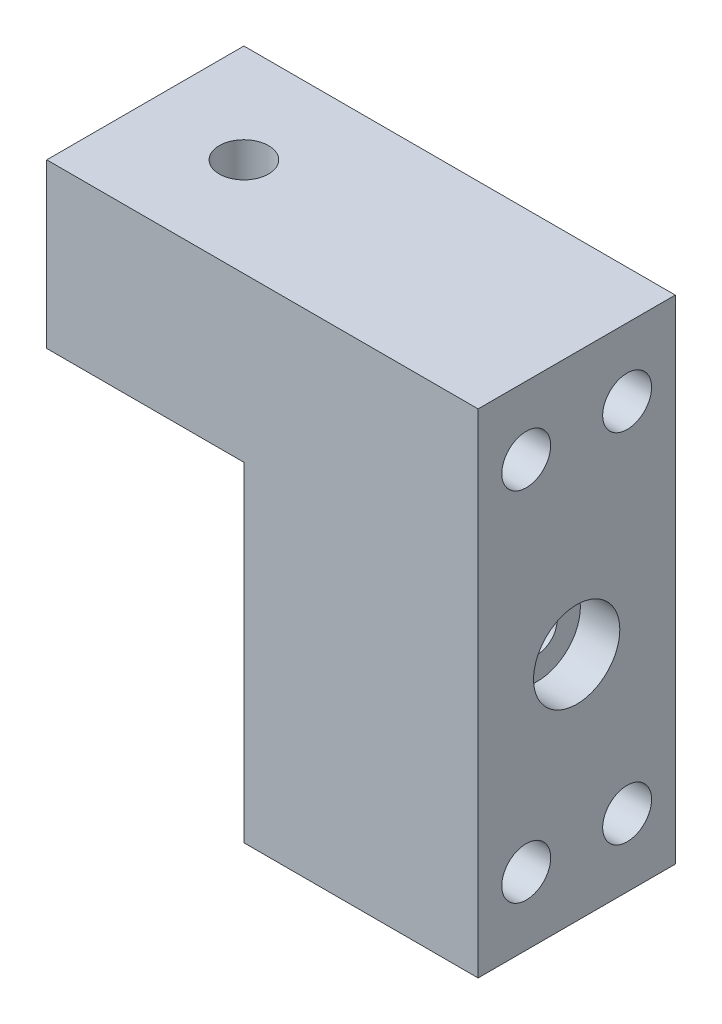
SolidWorks part; units mm, degrees
material "McMaster 6061-T6"
ref_plane "Front Plane" through (0, 0, 0) normal (0, 0, 1) x (1, 0, 0)
ref_plane "Top Plane" through (0, 0, 0) normal (0, 1, 0) x (1, 0, 0)
ref_plane "Right Plane" through (0, 0, 0) normal (1, 0, 0) x (0, 0, -1)
sketch "Sketch2" plane through (0, 0, 0) normal (1, 0, 0) x (0, 0, -1)
  line L1 (-212.3494, -348.1117) -> (-237.7494, -348.1117)
  line L2 (-212.3494, -348.1117) -> (-212.3494, -411.6117)
  line L3 (-212.3494, -411.6117) -> (-237.7494, -411.6117)
  line L4 (-237.7494, -348.1117) -> (-237.7494, -411.6117)
  dimension "D1" = 25.4
  dimension "D2" = 63.5
extrude "Boss-Extrude1" add sketch "Sketch2" against normal up to surface (30.176 mm away)
sketch "Sketch3" plane through (-30.176, 0, 0) normal (-1, 0, 0) x (0, 0, 1)
  line L0 (212.3494, -348.1117) -> (212.3494, -411.6117) construction
  line L1 (237.7494, -348.1117) -> (212.3494, -348.1117)
  line L2 (237.7494, -348.1117) -> (237.7494, -369.1617)
  line L3 (237.7494, -369.1617) -> (212.3494, -369.1617)
  line L4 (212.3494, -348.1117) -> (212.3494, -369.1617)
  line L5 (-189.9139, -369.1617) -> (707.5494, -369.1617) construction
extrude "Boss-Extrude2" add sketch "Sketch3" along normal blind 25.4
sketch "Sketch6" plane through (0, -348.1117, 0) normal (0, 1, 0) x (1, 0, 0)
  line L0 (-42.876, -237.7494) -> (-42.876, -212.3494) construction
  line L1 (-55.576, -237.7494) -> (0, -237.7494) construction
  line L2 (-55.576, -212.3494) -> (0, -212.3494) construction
  line L3 (-55.576, -237.7494) -> (-55.576, -212.3494) construction
  point P8 (-42.876, -225.0494)
  dimension "D1" = 12.7
hole_wizard "1/4 (0.25) Diameter Hole1" positions "Sketch7" profile "Sketch9" hole size "1/4" standard "ANSI Inch" end condition through all
sketch "Sketch7" plane through (0, -348.1117, 0) normal (0, 1, 0) x (1, 0, 0)
  point P0 (-42.876, -225.0494)
sketch "Sketch9" plane through (-42.876, -348.1117, 225.0494) normal (1, 0, 0) x (0, 0, 1)
  line L0 (0, 0) -> (0, 63.5)
  line L1 (0, 63.5) -> (3.175, 63.5)
  line L2 (3.175, 63.5) -> (3.175, 0)
  line L5 (3.175, 0) -> (0, 0)
  line L11 (0, -6.35) -> (0, 107.95) construction
  dimension "Thru Hole Dia." = 6.35
  dimension "Thru Hole Depth" = 63.5
hole_wizard "Ø1.0mm Dowel Hole1" positions "Sketch12" profile "Sketch13" hole size "Ø1.0" standard "ANSI Metric"
sketch "Sketch12" plane through (0, 0, 0) normal (1, 0, 0) x (0, 0, -1)
  circle A0 centre (-218.5494, -402.8617) radius 5 construction
  circle A1 centre (-231.5494, -402.8617) radius 4.4 construction
  point P0 (-231.5494, -356.8617)
  point P3 (-218.5494, -356.8617)
  point P6 (-218.5494, -402.8617)
  point P8 (-231.5494, -402.8617)
sketch "Sketch13" plane through (0, -356.8617, 231.5494) normal (0, 1, 0) x (0, 0, -1)
  line L0 (0, 0) -> (0, 10.8843)
  line L1 (0, 10.8843) -> (3.15, 8.9916)
  line L2 (3.15, 8.9916) -> (3.15, 0)
  line L5 (3.15, 0) -> (0, 0)
  line L10 (0, 10.8843) -> (-3.15, 8.9916) construction
  line L11 (0, -6.35) -> (0, 107.95) construction
  dimension "Hole Dia." = 6.3
  dimension "Hole Depth" = 8.9916
  dimension "Drill Angle" = 118
hole_wizard "Tap Drill for #5 Helicoil0" positions "Sketch14" profile "Sketch15" hole size "Ø4.0" standard "ANSI Metric"
sketch "Sketch14" plane through (0, 0, 212.3494) normal (0, 0, -1) x (-1, 0, 0)
  point P0 (9.7875, -371.9242)
  point P3 (9.7875, -387.7992)
sketch "Sketch15" plane through (-9.7875, -371.9242, 212.3494) normal (1, 0, 0) x (0, 1, 0)
  line L0 (0, 0) -> (0, 16.4417)
  line L1 (0, 16.4417) -> (2, 15.24)
  line L2 (2, 15.24) -> (2, 0)
  line L5 (2, 0) -> (0, 0)
  line L10 (0, 16.4417) -> (-2, 15.24) construction
  line L11 (0, -6.35) -> (0, 107.95) construction
  dimension "Hole Dia." = 4
  dimension "Hole Depth" = 15.24
  dimension "Drill Angle" = 118
hole_wizard "CBORE for #10 Binding Head Machine Screw1" positions "Sketch17" profile "Sketch18" counterbore size "#10" standard "ANSI Inch" end condition up to next
sketch "Sketch17" plane through (0, 0, 0) normal (1, 0, 0) x (0, 0, -1)
  line L0 (-212.3494, -381.8617) -> (-237.7494, -381.8617) construction
  line L1 (-212.3494, -411.6117) -> (-212.3494, -348.1117) construction
  line L2 (-237.7494, -348.1117) -> (-237.7494, -411.6117) construction
  point P0 (-225.0494, -381.8617)
sketch "Sketch18" plane through (0, -381.8617, 225.0494) normal (0, 1, 0) x (0, 0, -1)
  line L0 (0, 0) -> (0, 30.176)
  line L1 (0, 30.176) -> (2.5527, 30.176)
  line L3 (2.5527, 30.176) -> (2.5527, 5.08)
  line L4 (2.5527, 5.08) -> (5.5562, 5.08)
  line L5 (5.5562, 5.08) -> (5.5562, 0)
  line L7 (5.5562, 0) -> (0, 0)
  line L11 (0, -6.35) -> (0, 107.95) construction
  dimension "Thru Hole Dia." = 5.1054
  dimension "Thru Hole Depth" = 30.176
  dimension "C'Bore Dia." = 11.1125
  dimension "C'Bore Depth" = 5.08
